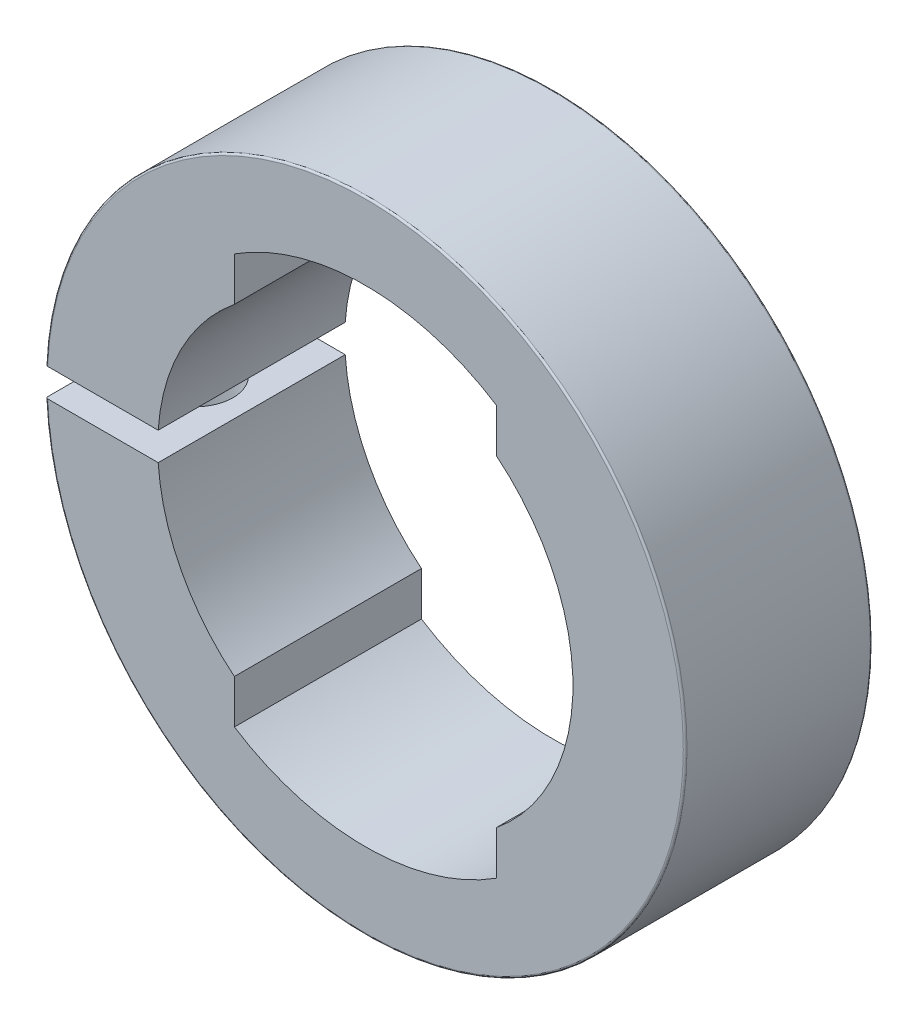
SolidWorks part; units mm, degrees
material "6061-T4 (SS)"
ref_plane "Front Plane" through (0, 0, 0) normal (0, 0, 1) x (1, 0, 0)
ref_plane "Top Plane" through (0, 0, 0) normal (0, 1, 0) x (1, 0, 0)
ref_plane "Right Plane" through (0, 0, 0) normal (1, 0, 0) x (0, 0, -1)
sketch "Sketch1" plane through (0, 0, 0) normal (0, 0, 1) x (1, 0, 0)
  line L0 (-7, 10.9545) -> (-7, 8.6145)
  line L1 (7, 10.9545) -> (7, 8.6145)
  line L2 (-7, -8.6145) -> (-7, -10.9545)
  line L3 (7, -8.6145) -> (7, -10.9545)
  line L4 (-17.0835, 0.75) -> (-11.0746, 0.75)
  line L5 (-17.0835, -0.75) -> (-11.0746, -0.75)
  line L6 (0, 0) -> (-7.7467, 0) construction
  arc A0 (-7, 8.6145) -> (-11.0746, 0.75) centre (0, 0) ccw
  arc A1 (-17.0835, -0.75) -> (-17.0835, 0.75) centre (0, 0) ccw
  arc A2 (-7, -10.9545) -> (7, -10.9545) centre (0, 0) ccw
  arc A3 (7, 10.9545) -> (-7, 10.9545) centre (0, 0) ccw
  circle A4 centre (0, 0) radius 11.1 construction
  arc A5 (7, -8.6145) -> (7, 8.6145) centre (0, 0) ccw
  circle A6 centre (0, 0) radius 17.1 construction
  arc A7 (-11.0746, -0.75) -> (-7, -8.6145) centre (0, 0) ccw
  dimension "D1" = 22.2
  dimension "D3" = 26
  dimension "D4" = 14
  dimension "D5" = 1.5
  dimension "D2" = 6
extrude "Boss-Extrude1" add sketch "Sketch1" along normal blind 10
sketch "Sketch2" plane through (0, -0.75, 0) normal (0, 1, 0) x (1, 0, 0)
  line L0 (-14.0791, 0) -> (-14.0791, -10) construction
  line L1 (-11.0746, 0) -> (-17.0835, 0) construction
  line L2 (-11.0746, -10) -> (-17.0835, -10) construction
  line L3 (-11.0746, -5) -> (-17.0835, -5) construction
  line L4 (-11.0746, -10) -> (-11.0746, 0) construction
  line L5 (-17.0835, -10) -> (-17.0835, 0) construction
  circle A0 centre (-14.0791, -5) radius 2
  dimension "D1" = 4
extrude "Cut-Extrude1" cut sketch "Sketch2" against normal through all both and the other way through all
fillet "Fillet1" radius 0.1 2 edges at (17.1, 0, 0) (17.1, 0, 10)
